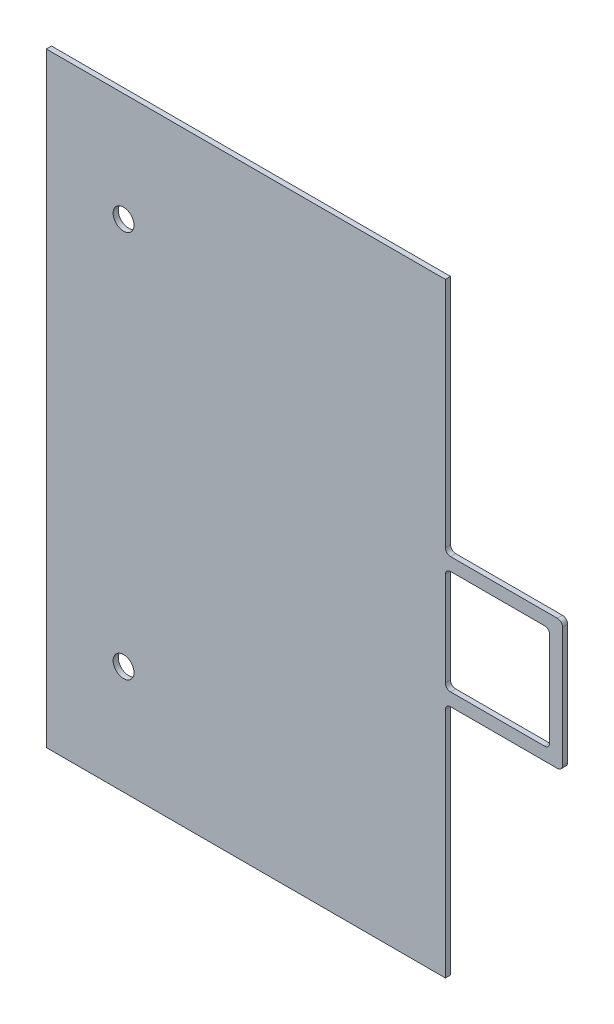
SolidWorks part; units mm, degrees
ref_plane "Ön Düzlem" through (0, 0, 0) normal (0, 0, 1) x (1, 0, 0)
ref_plane "Üst Düzlem" through (0, 0, 0) normal (0, 1, 0) x (1, 0, 0)
ref_plane "Sağ Düzlem" through (0, 0, 0) normal (1, 0, 0) x (0, 0, -1)
sketch "Sketch9" plane through (0, 0, 0) normal (0, 0, 1) x (1, 0, 0)
  line L0 (159, 40.5) -> (232, 40.5)
  line L1 (-155, -235) -> (155, -235)
  line L2 (-155, -235) -> (-155, 235)
  line L3 (-155, 235) -> (155, 235)
  line L4 (155, -235) -> (155, -54.5)
  line L5 (-155, -235) -> (155, 235) construction
  line L6 (-155, 235) -> (155, -235) construction
  line L7 (236, 36.5) -> (236, -36.5)
  line L8 (232, -40.5) -> (159, -40.5)
  line L9 (159, 50.5) -> (242, 50.5)
  line L10 (246, 46.5) -> (246, -46.5)
  line L11 (242, -50.5) -> (159, -50.5)
  line L12 (155, 54.5) -> (155, 235)
  line L13 (155, -36.5) -> (155, 36.5)
  line L14 (155, 0) -> (-95, 0) construction
  line L15 (-95, 150.5) -> (-95, -150.5) construction
  arc A0 (159, -40.5) -> (155, -36.5) centre (159, -36.5) cw
  arc A1 (236, -36.5) -> (232, -40.5) centre (232, -36.5) cw
  arc A2 (232, 40.5) -> (236, 36.5) centre (232, 36.5) cw
  arc A3 (159, 40.5) -> (155, 36.5) centre (159, 36.5) ccw
  arc A4 (159, 50.5) -> (155, 54.5) centre (159, 54.5) cw
  arc A5 (159, -50.5) -> (155, -54.5) centre (159, -54.5) ccw
  arc A6 (246, -46.5) -> (242, -50.5) centre (242, -46.5) cw
  arc A7 (242, 50.5) -> (246, 46.5) centre (242, 46.5) cw
  circle A8 centre (-95, 150.5) radius 8.1
  circle A9 centre (-95, -150.5) radius 8.1
  point P0 (0, 0)
  point P17 (155, -40.5)
  point P22 (236, 40.5)
  point P25 (155, 40.5)
  point P28 (155, 50.5)
  point P33 (246, -50.5)
  point P36 (246, 50.5)
  point P41 (-95, 0)
  point P44 (246, 0)
  point P45 (-95, 0)
  dimension "D6" = 4
  dimension "D7" = 4
  dimension "D10" = 16.2
  dimension "D1" = 470
  dimension "D2" = 310
  dimension "D3" = 81
  dimension "D4" = 91
  dimension "D5" = 101
  dimension "D8" = 250
  dimension "D9" = 301
base flange "Base-Flange2" sketch "Sketch9" thickness 4 reverse thickness direction no parameters "D1"=0.7366
sketch "Büküm-Çizgileri3" [suppressed] plane through (0, 0, 0) normal (0, 1, 0) x (1, 0, 0)
sketch "Sınırlandırma-Kutusu3" [suppressed] plane through (0, 0, 0) normal (0, 1, 0) x (1, 0, 0)
sheet metal parameters "Sac-Levha2" thickness 4 parameters "D1"=0.7366
flat pattern "Düz-Çoğaltma2" [suppressed]
sketch "Büküm-Çizgileri4" plane through (0, 0, 0) normal (0, 1, 0) x (1, 0, 0)
sketch3d "Sınırlandırma-Kutusu4" [suppressed]
  line L0 (86.9998, -180.5001, 0) -> (87.0001, 289.4999, 0) construction
  line L1 (-314, -180.4998, 0) -> (-313.9997, 289.5002, 0) construction
  line L2 (86.9998, -180.5001, 0) -> (-314, -180.4998, 0) construction
  line L3 (87.0001, 289.4999, 0) -> (-313.9997, 289.5002, 0) construction
